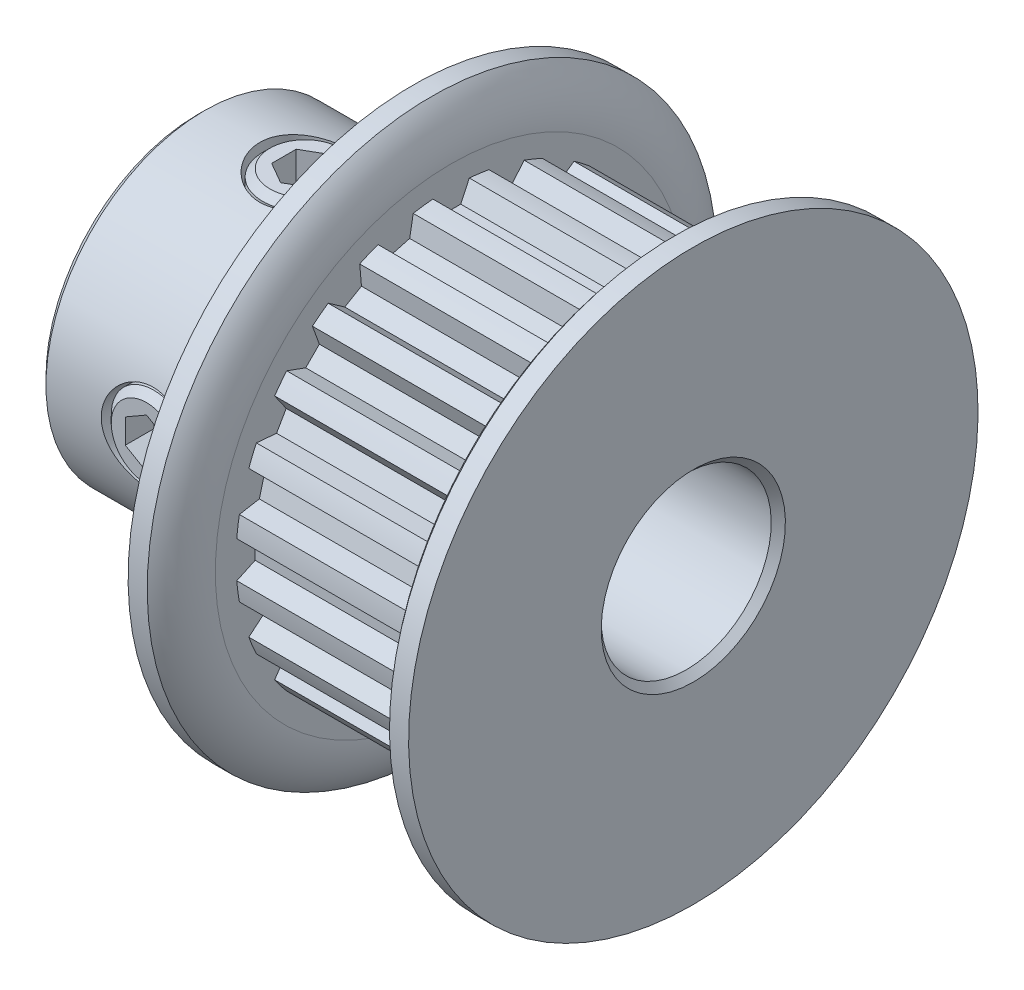
SolidWorks part; units mm, degrees
ref_plane "Front Plane" through (0, 0, 0) normal (0, 0, 1) x (1, 0, 0)
ref_plane "Top Plane" through (0, 0, 0) normal (0, 1, 0) x (1, 0, 0)
ref_plane "Right Plane" through (0, 0, 0) normal (1, 0, 0) x (0, 0, -1)
sketch "Sketch2" plane through (0, 0, 0) normal (1, 0, 0) x (0, 0, -1)
  line L3 (0, 0) -> (0, 6.9245) construction
  line L6 (0, -7.4325) -> (0, -7.75) construction
  line L7 (-0.5715, 7.4105) -> (-0.341, 6.9161)
  line L8 (0.5715, 7.4105) -> (0.341, 6.9161)
  line L9 (-0.5715, 7.4105) -> (-0.6431, 7.564)
  line L10 (0.5715, 7.4105) -> (0.6431, 7.564)
  line L12 (-0.341, 6.9161) -> (0.341, 6.9161)
  line L14 (0, 7.4325) -> (0, 7.75) construction
  line L15 (0, 0) -> (0, -1.143) construction
  circle A0 centre (0, 0) radius 7.75 construction
  circle A1 centre (0, 0) radius 6.9245 construction
  circle A2 centre (0, 0) radius 7.4325 construction
  arc A7 (0.6431, 7.564) -> (-0.6431, 7.564) centre (0, 0) ccw
  point P5 (0, 7.5912)
  dimension "D3" = 0.3175
  dimension "D1" = 50
sketch "Sketch1" plane through (0, 0, 0) normal (0, 0, 1) x (1, 0, 0)
  line L0 (-8.75, 0) -> (8.75, 0) construction
  line L1 (-8.75, 3) -> (8.75, 3)
  line L2 (-8.75, 3) -> (-8.75, 5.6)
  line L3 (-1.15, 10.05) -> (-0.475, 10.05)
  line L4 (0.2, 7.75) -> (0.2, 8.3215)
  line L5 (0.2, 8.893) -> (0.2, 7.75) construction
  line L6 (0.2, 7.75) -> (7.4, 7.75)
  line L7 (7.4, 7.75) -> (7.4, 8.3215)
  line L8 (7.4, 7.75) -> (8.75, 7.75) construction
  line L9 (8.075, 10.05) -> (8.75, 10.05)
  line L10 (8.75, 10.05) -> (8.75, 3)
  line L11 (8.075, 7.75) -> (8.075, 10.05) construction
  line L12 (-4.95, 5.6) -> (-4.95, 3) construction
  line L13 (-1.15, 10.05) -> (-1.15, 5.6)
  line L14 (-1.15, 5.6) -> (-8.75, 5.6)
  arc A0 (7.4, 8.3215) -> (8.075, 10.05) centre (9.9506, 8.3215) cw
  arc A1 (0.2, 8.3215) -> (-0.475, 10.05) centre (-2.3506, 8.3215) ccw
  dimension "Bore Size" = 6
  dimension "Overall Width" = 17.5
  dimension "Inside Width" = 7.2
  dimension "OD" = 20.1
  dimension "D2" = 15.5
  dimension "D3" = 1.143
  dimension "D4" = 0.5715
  dimension "Outside Width" = 9.9
revolve "Revolve1" add sketch "Sketch1" angle 360 mid plane about L0
sketch "Sketch4" plane through (0.2, 0, 0) normal (1, 0, 0) x (0, 0, -1)
  circle A0 centre (0, 0) radius 7.5913
  circle A2 centre (0, 0) radius 7.75
  circle A3 centre (0, 0) radius 7.75 construction
extrude "Cut-Extrude2" cut sketch "Sketch4" along normal up to surface (7.2 mm away) up to face at (7.4, -7.75, 0)
sketch "Sketch3" plane through (0.2, 0, 0) normal (1, 0, 0) x (0, 0, -1)
  line L2 (-0.5715, 7.4105) -> (-0.341, 6.9161) construction
  line L3 (-0.341, 6.9161) -> (0.341, 6.9161) construction
  line L4 (0.5715, 7.4105) -> (0.341, 6.9161) construction
  line L5 (-0.6431, 7.564) -> (-0.341, 6.9161)
  line L6 (-0.341, 6.9161) -> (0.341, 6.9161)
  line L7 (0.6431, 7.564) -> (0.341, 6.9161)
  arc A1 (0.6431, 7.564) -> (-0.6431, 7.564) centre (0, 0) ccw construction
  arc A2 (0.6431, 7.564) -> (-0.6431, 7.564) centre (0, 0) ccw
extrude "Cut-Extrude1" cut sketch "Sketch3" along normal up to surface (7.2 mm away)
pattern_circular "CirPattern1" count 24 over 360 of "Cut-Extrude1"
sketch "Sketch5" plane through (0, 0, 0) normal (0, 0, 1) x (1, 0, 0)
  line L1 (7.4, 8.3215) -> (7.4, -8.3215) construction
  point P0 (7.4, 0)
sketch "Sketch6" plane through (0, 0, 0) normal (0, 1, 0) x (1, 0, 0)
  line L0 (-8.75, 0) -> (-6.45, 0) construction
  line L1 (-8.75, 10.05) -> (-8.75, -10.05) construction
  line L2 (-1.15, 0) -> (-3.45, 0) construction
  line L4 (-1.15, 10.05) -> (-1.15, -10.05) construction
  circle A0 centre (-4.95, 0) radius 1.5 construction
  circle A1 centre (-4.95, 0) radius 1.6
  dimension "D1" = 0.1
  dimension "SS Dia" = 3
extrude "Cut-Extrude3" cut sketch "Sketch6" along normal through all
sketch "Sketch7" plane through (0, 0, 0) normal (0, 0, 1) x (1, 0, 0)
  line L0 (-6.196, 5.6) -> (-4.95, 5.6)
  line L1 (-6.45, 5.346) -> (-6.45, 3.635)
  line L2 (-6.45, 3.635) -> (-6.196, 3.381)
  line L3 (-6.196, 3.381) -> (-4.95, 3.381)
  line L4 (-4.95, 3.381) -> (-4.95, 5.6) construction
  line L5 (-1.15, 5.6) -> (-8.75, 5.6) construction
  line L6 (-6.45, 5.346) -> (-6.196, 5.6)
  line L8 (-4.95, 5.6) -> (-4.95, 3.381)
  point P0 (-6.45, 5.6)
  point P4 (-6.45, 3.381)
  dimension "D2" = 0.381
revolve "Revolve2" add sketch "Sketch7" angle 360 mid plane about L4
sketch "Sketch8" plane through (0, 5.6, 0) normal (0, 1, 0) x (1, 0, 0)
  line L1 (-4.95, 0.866) -> (-5.7, 0.433)
  line L2 (-5.7, 0.433) -> (-5.7, -0.433)
  line L3 (-5.7, -0.433) -> (-4.95, -0.866)
  line L4 (-4.95, -0.866) -> (-4.2, -0.433)
  line L5 (-4.2, -0.433) -> (-4.2, 0.433)
  line L6 (-4.2, 0.433) -> (-4.95, 0.866)
  circle A0 centre (-4.95, 0) radius 0.75 construction
  dimension "D1" = 1.5
extrude "Cut-Extrude4" cut sketch "Sketch8" against normal blind 1.016
pattern_circular "CirPattern2" count 2 over 90 about axis through (-8.75, 0, 0) along (-1, 0, 0) of "Cut-Extrude3" reverse direction yes
pattern_circular "CirPattern3" count 2 over 90 reverse direction yes of bodies 107
chamfer "Chamfer1" distance 0.25 angle 45 3 edges at (-8.75, -5.6, 0) (8.75, -3, 0) (-8.75, -3, 0)
ref_axis "Center Axis 1" through (8.5, 0, 0) along (-1, 0, 0)
ref_plane "Contact Plane 1" through (-8.75, 0, 0) normal (-1, 0, 0) x (0, 0, 1)
ref_plane "Contact Plane 2" through (8.75, 0, 0) normal (1, 0, 0) x (0, 0, -1)
equation "\"D3@Sketch2\" = (\"hs@Sketch2\"-\"ht@Sketch2\")/2"
equation "\"D2@Sketch1\" = \"PD@Sketch2\""
equation "\"D3@Sketch1\" = \"hs@Sketch2\""
equation "\"D4@Sketch1\" = \"D3@Sketch1\"/2"
